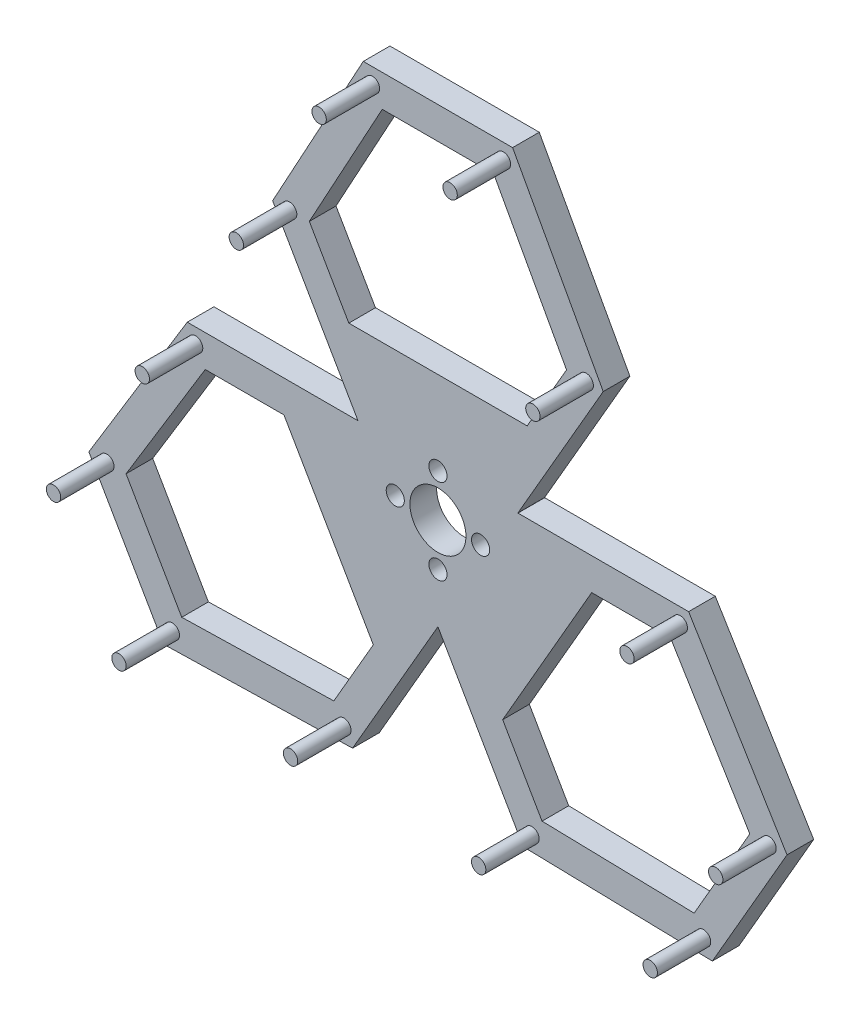
SolidWorks part; units mm, degrees
ref_plane "Front Plane" through (0, 0, 0) normal (0, 0, 1) x (1, 0, 0)
ref_plane "Top Plane" through (0, 0, 0) normal (0, 1, 0) x (1, 0, 0)
ref_plane "Right Plane" through (0, 0, 0) normal (1, 0, 0) x (0, 0, -1)
sketch "Sketch1" plane through (0, 0, 0) normal (0, 0, 1) x (1, 0, 0)
  line L0 (0, 17.3205) -> (0, 67.5) construction
  line L1 (15, 8.6603) -> (10, 17.3205) construction
  line L2 (0, 17.3205) -> (-10, 17.3205) construction
  line L3 (-15, 8.6603) -> (-20, 0) construction
  line L4 (-20, 0) -> (-15, -8.6603) construction
  line L5 (-10, -17.3205) -> (0, -17.3205) construction
  line L6 (15, -8.6603) -> (20, 0) construction
  line L7 (77.9423, 0) -> (38.9711, 67.5) construction
  line L8 (38.9711, 67.5) -> (-38.9711, 67.5) construction
  line L9 (-38.9711, 67.5) -> (-77.9423, 0) construction
  line L10 (-77.9423, 0) -> (-38.9711, -67.5) construction
  line L11 (-38.9711, -67.5) -> (38.9711, -67.5) construction
  line L12 (38.9711, -67.5) -> (77.9423, 0) construction
  line L14 (-30.995, 36.3817) -> (-14, 67.5)
  line L18 (10, 17.3205) -> (0, 17.3205) construction
  line L19 (-15, -8.6603) -> (-10, -17.3205) construction
  line L20 (10, -17.3205) -> (15, -8.6603) construction
  line L21 (-10, 17.3205) -> (-15, 8.6603) construction
  line L22 (20, 0) -> (15, 8.6603) construction
  line L23 (0, -17.3205) -> (10, -17.3205) construction
  line L24 (-10, 17.3205) -> (-14.995, 8.6689) construction
  line L25 (-15, 8.6603) -> (-14.995, 8.6689)
  line L26 (-14.995, 8.6689) -> (-30.995, 36.3817)
  line L27 (14, 67.5) -> (-14, 67.5)
  line L28 (30.995, 36.3817) -> (14, 67.5)
  line L29 (14.995, 8.6689) -> (30.995, 36.3817)
  line L30 (15, 8.6603) -> (14.995, 8.6689)
  line L31 (15, 8.6603) -> (15.005, 8.6516)
  line L32 (15.005, 8.6516) -> (47.005, 8.6516)
  line L33 (47.005, 8.6516) -> (65.4567, -21.6256)
  line L34 (51.4567, -45.8744) -> (65.4567, -21.6256)
  line L35 (16.01, -45.0333) -> (51.4567, -45.8744)
  line L36 (0.01, -17.3205) -> (16.01, -45.0333)
  line L37 (0, -17.3205) -> (0.01, -17.3205)
  line L38 (0, -17.3205) -> (-0.01, -17.3205)
  line L39 (-0.01, -17.3205) -> (-16.01, -45.0333)
  line L40 (-16.01, -45.0333) -> (-51.4567, -45.8744)
  line L41 (-65.4567, -21.6256) -> (-51.4567, -45.8744)
  line L42 (-47.005, 8.6516) -> (-65.4567, -21.6256)
  line L43 (-15.005, 8.6516) -> (-47.005, 8.6516)
  line L44 (-15, 8.6603) -> (-15.005, 8.6516)
  arc A0 (15, 8.6603) -> (0, 17.3205) centre (0, 0) ccw construction
  circle A1 centre (0, 0) radius 67.5 construction
  arc A2 (15, -8.6603) -> (15, 8.6603) centre (0, 0) ccw construction
  arc A3 (0, -17.3205) -> (15, -8.6603) centre (0, 0) ccw construction
  arc A4 (0, 17.3205) -> (-15, 8.6603) centre (0, 0) ccw construction
  arc A5 (-15, -8.6603) -> (0, -17.3205) centre (0, 0) ccw construction
  arc A6 (-15, 8.6603) -> (-15, -8.6603) centre (0, 0) ccw construction
  point P47 (0, 0)
  dimension "D1" = 20
  dimension "D2" = 135
  dimension "D3" = 14
  dimension "D4" = 9.99
  dimension "D5" = 32
  dimension "D6" = 120
  dimension "D7" = 3
extrude "Boss-Extrude1" add sketch "Sketch1" along normal blind 5
sketch "Sketch2" plane through (0, 0, 5) normal (0, 0, 1) x (1, 0, 0)
  line L0 (-15.005, 8.6516) -> (0.01, -17.3205) construction
  line L1 (-20.4956, -11.8211) -> (-7.4975, -4.3345) construction
  line L2 (-15.005, 8.6516) -> (15.005, 8.6516) construction
  line L3 (15.005, 8.6516) -> (0.01, -17.3205) construction
  line L5 (-28.8721, 2.6516) -> (-12.119, -26.2939)
  line L20 (-19.5212, -39.1149) -> (-5.2062, -14.3205)
  line L21 (-48.0404, -39.7916) -> (-19.5212, -39.1149)
  line L22 (-58.4807, -21.7084) -> (-48.0404, -39.7916)
  line L23 (-43.6351, 2.6516) -> (-58.4807, -21.7084)
  line L24 (-15.005, 2.6516) -> (-43.6351, 2.6516)
  line L25 (-19.5212, -39.1149) -> (-12.119, -26.2939)
  line L26 (-48.0404, -39.7916) -> (-19.5212, -39.1149)
  line L27 (-58.4807, -21.7084) -> (-48.0404, -39.7916)
  line L28 (-43.6351, 2.6516) -> (-58.4807, -21.7084)
  line L29 (-28.8721, 2.6516) -> (-43.6351, 2.6516)
  line L31 (-24.1139, 36.4633) -> (-16.7117, 23.6423)
  line L32 (16.7324, 23.6782) -> (-16.7117, 23.6423)
  line L33 (16.7324, 23.6782) -> (24.1139, 36.4633)
  line L34 (24.1139, 36.4633) -> (10.4404, 61.5)
  line L35 (10.4404, 61.5) -> (-10.4404, 61.5)
  line L36 (-10.4404, 61.5) -> (-24.1139, 36.4633)
  line L37 (43.6351, 2.6516) -> (28.8306, 2.6516)
  line L38 (12.1397, -26.3298) -> (28.8306, 2.6516)
  line L39 (12.1397, -26.3298) -> (19.5212, -39.1149)
  line L40 (19.5212, -39.1149) -> (48.0404, -39.7916)
  line L41 (48.0404, -39.7916) -> (58.4807, -21.7084)
  line L42 (58.4807, -21.7084) -> (43.6351, 2.6516)
  point P31 (0, -1.1576)
  point P32 (0, 0)
  dimension "D2" = 15
  dimension "D1" = 6
  dimension "D3" = 3
extrude "Cut-Extrude1" cut sketch "Sketch2" against normal through all
sketch "Sketch3" plane through (0, 0, 0) normal (0, 0, -1) x (-1, 0, 0)
  circle A0 centre (0, 0) radius 5.25
  dimension "D1" = 10.5
extrude "Cut-Extrude2" cut sketch "Sketch3" against normal up to surface (5 mm away) up to face at (35.108, -20.2736, 5)
sketch "Sketch5" plane through (0, 0, 5) normal (0, 0, 1) x (1, 0, 0)
  line L0 (-47.005, 8.6516) -> (-43.8811, 3.0895) construction
  line L1 (-65.4567, -21.6256) -> (-58.7141, -21.7056) construction
  line L2 (-51.4567, -45.8744) -> (-48.1547, -39.9951) construction
  line L3 (-16.01, -45.0333) -> (-19.265, -39.5469) construction
  line L4 (30.995, 36.3817) -> (24.6161, 36.4574) construction
  line L5 (14, 67.5) -> (10.5594, 61.7007) construction
  line L6 (-14, 67.5) -> (-10.5594, 61.7007) construction
  line L7 (-30.995, 36.3817) -> (-24.6161, 36.4574) construction
  line L8 (16.01, -45.0333) -> (19.265, -39.5469) construction
  line L9 (51.4567, -45.8744) -> (48.1547, -39.9951) construction
  line L10 (65.4567, -21.6256) -> (58.7141, -21.7056) construction
  line L11 (47.005, 8.6516) -> (43.8811, 3.0895) construction
  circle A0 centre (-45.443, 5.8705) radius 1.35
  circle A1 centre (-62.0854, -21.6656) radius 1.35
  circle A2 centre (-49.8057, -42.9347) radius 1.35
  circle A3 centre (-17.6375, -42.2901) radius 1.35
  circle A4 centre (27.8056, 36.4196) radius 1.35
  circle A5 centre (12.2797, 64.6003) radius 1.35
  circle A6 centre (-12.2797, 64.6003) radius 1.35
  circle A7 centre (-27.8056, 36.4196) radius 1.35
  circle A8 centre (17.6375, -42.2901) radius 1.35
  circle A9 centre (49.8057, -42.9347) radius 1.35
  circle A10 centre (62.0854, -21.6656) radius 1.35
  circle A11 centre (45.443, 5.8705) radius 1.35
  point P48 (0, 0)
  point P49 (0, 0)
  point P50 (0, 0)
  point P51 (0, 0)
  dimension "D1" = 2.7
extrude "Boss-Extrude2" add sketch "Sketch5" along normal blind 10
sketch "Sketch6" plane through (0, 0, 0) normal (0, 0, -1) x (-1, 0, 0)
  line L0 (0, 8) -> (0, -8) construction
  line L1 (8, 0) -> (-8, 0) construction
  circle A0 centre (-8, 0) radius 1.7
  circle A1 centre (0, -8) radius 1.7
  circle A2 centre (8, 0) radius 1.7
  circle A3 centre (0, 8) radius 1.7
  point P3 (0, 0)
  point P7 (0, 0)
  dimension "D2" = 3.4
  dimension "D1" = 16
extrude "Cut-Extrude3" cut sketch "Sketch6" against normal up to surface (5 mm away) up to face at (46.793, 5.8705, 5)
